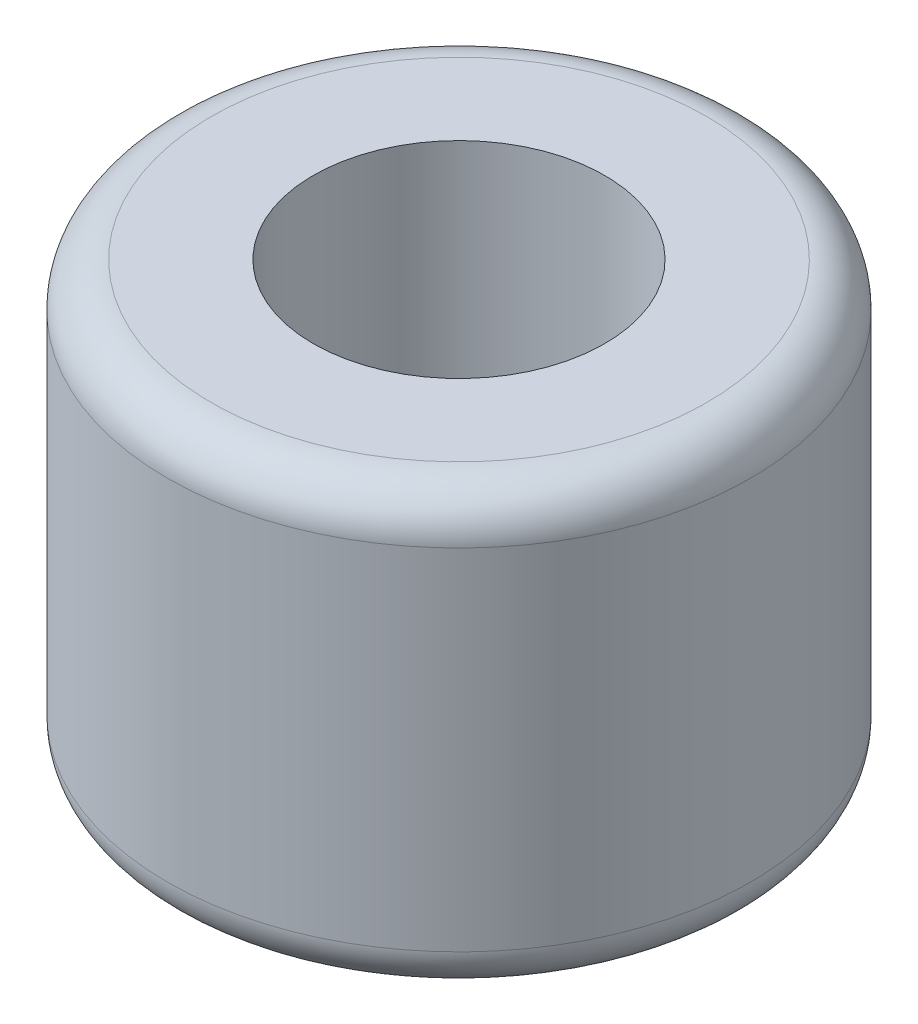
SolidWorks part; units mm, degrees
ref_plane "Front Plane" through (0, 0, 0) normal (0, 0, 1) x (1, 0, 0)
ref_plane "Top Plane" through (0, 0, 0) normal (0, 1, 0) x (1, 0, 0)
ref_plane "Right Plane" through (0, 0, 0) normal (1, 0, 0) x (0, 0, -1)
sketch "Sketch1" plane through (0, 0, 0) normal (0, 0, 1) x (1, 0, 0)
  line L0 (0, 0) -> (0, 25.4)
  line L1 (0, 25.4) -> (50.8, 25.4)
  line L2 (50.8, 25.4) -> (50.8, 152.4)
  line L3 (50.8, 152.4) -> (101.6, 152.4)
  line L4 (101.6, 152.4) -> (101.6, 0)
  line L5 (101.6, 0) -> (0, 0)
  dimension "D1" = 101.6
  dimension "D2" = 25.4
  dimension "D3" = 152.4
  dimension "D4" = 50.8
revolve "Revolve1" add sketch "Sketch1" angle 360 about L0 reverse direction yes
sketch "Sketch2" plane through (0, 0, 0) normal (0, -1, 0) x (1, 0, 0)
  line L0 (0, 101.6) -> (0, -101.6) construction
  line L1 (-101.6, 0) -> (101.6, 0) construction
  circle A0 centre (0, 0) radius 101.6 construction
  circle A1 centre (-76.2, 0) radius 12.7
  circle A2 centre (76.2, 0) radius 12.7
  dimension "D1" = 25.4
  dimension "D2" = 76.2
extrude "Cut-Extrude1" cut sketch "Sketch2" against normal blind 76.2 from offset 12.7
fillet "Fillet2" radius 15.24 2 edges at (0, 0, 101.6) (0, 152.4, 101.6)
